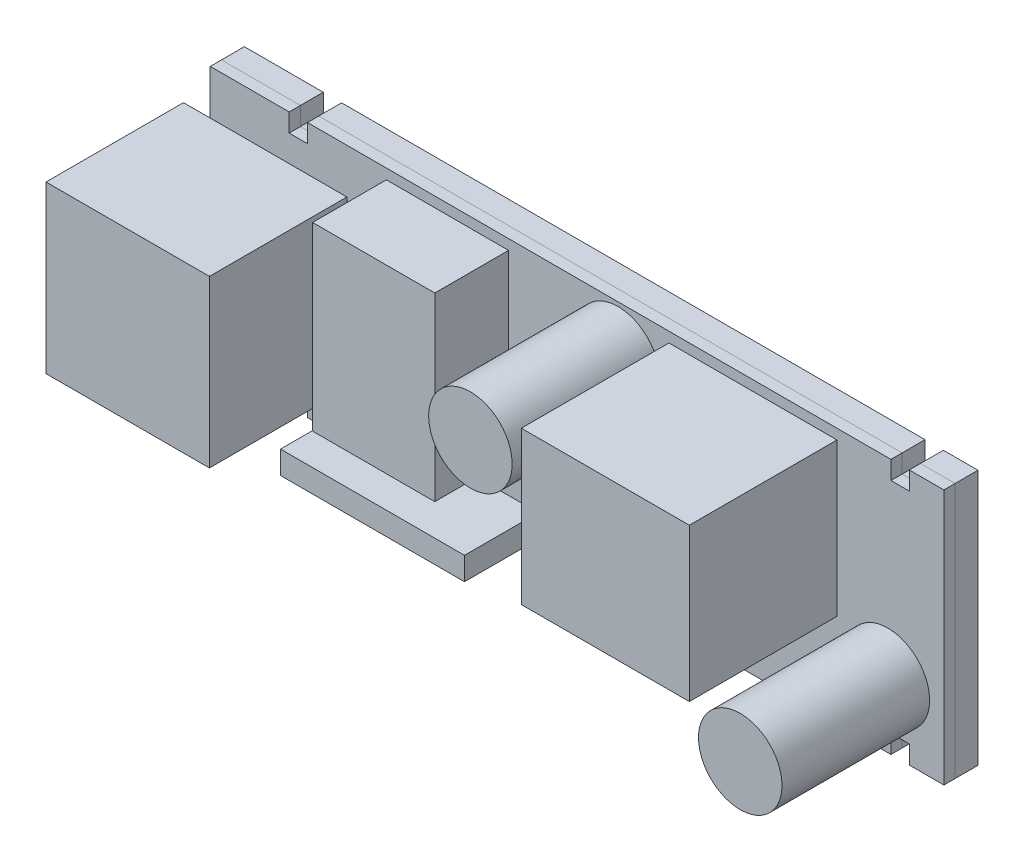
SolidWorks part; units mm, degrees
note: The reader was unsure of these and kept them because the rebuilt part matched: shared geometry of "Sketch1<3>", "Sketch2<4>", "Sketch2<5>".
ref_plane "Front Plane" through (0, 0, 0) normal (0, 0, 1) x (1, 0, 0)
ref_plane "Top Plane" through (0, 0, 0) normal (0, 1, 0) x (1, 0, 0)
ref_plane "Right Plane" through (0, 0, 0) normal (1, 0, 0) x (0, 0, -1)
sketch "Sketch1" plane through (0, 0, 0) normal (0, 0, 1) x (1, 0, 0)
  line L0 (-36.675, 12.55) -> (35.375, 12.55) construction
  line L1 (35.375, 12.55) -> (35.375, -12.55) construction
  line L2 (35.375, -12.55) -> (-36.675, -12.55) construction
  line L3 (-36.675, -12.55) -> (-36.675, 12.55) construction
  line L4 (-36.675, 12.55) -> (-36.675, -12.55)
  line L5 (-36.675, -12.55) -> (-28.925, -12.55)
  line L6 (-28.925, -12.55) -> (-28.925, -10.75)
  line L7 (-28.925, -10.75) -> (-27.125, -10.75)
  line L8 (-27.125, -10.75) -> (-27.125, -12.55)
  line L9 (-27.125, -12.55) -> (30.175, -12.55)
  line L10 (30.175, -12.55) -> (30.175, -10.75)
  line L11 (30.175, -10.75) -> (31.975, -10.75)
  line L12 (31.975, -10.75) -> (31.975, -12.55)
  line L13 (31.975, -12.55) -> (35.375, -12.55)
  line L14 (35.375, -12.55) -> (35.375, 12.55)
  line L15 (35.375, 12.55) -> (31.975, 12.55)
  line L16 (31.975, 12.55) -> (31.975, 10.75)
  line L17 (31.975, 10.75) -> (30.175, 10.75)
  line L18 (30.175, 10.75) -> (30.175, 12.55)
  line L19 (30.175, 12.55) -> (-27.125, 12.55)
  line L20 (-27.125, 12.55) -> (-27.125, 10.75)
  line L21 (-27.125, 10.75) -> (-28.925, 10.75)
  line L22 (-28.925, 10.75) -> (-28.925, 12.55)
  line L23 (-28.925, 12.55) -> (-36.675, 12.55)
  line L24 (35.375, 0) -> (0, 0) construction
  line L25 (39.6275, 0) -> (-39.6275, 0) construction
  line L26 (0, -13.805) -> (0, 13.805) construction
  circle A0 centre (0, 0) radius 1.375
  dimension "D7" = 2.75
  dimension "D1" = 1.8
  dimension "D2" = 1.8
  dimension "D3" = 3.4
  dimension "D4" = 7.75
  dimension "D5" = 25.1
  dimension "D6" = 72.05
  dimension "D8" = 35.375
extrude "Boss-BoardThk" add sketch "Sketch1" along normal blind 1.1 contours L19 L20 L21 L22 L23 L4 L5 L6 L7 L8 L9 L10 L11 L12 L13 L14 L15 L16 L17 L18 | A0
extrude "Boss-LowerClearance" add sketch "Sketch1<3>" against normal blind 2.25 separate body contours A0
sketch "Sketch1<3>" plane through (0, 0, 0) normal (0, 0, 1) x (1, 0, 0) same geometry as "Sketch1"
sketch "Sketch2" plane through (0, 0, 1.1) normal (0, 0, 1) x (1, 0, 0)
  line L0 (35.375, -12.55) -> (35.375, 12.55) construction
  line L1 (-19.375, 11.55) -> (-7.375, 11.55)
  line L2 (-19.375, 11.55) -> (-19.375, -6.2)
  line L3 (-19.375, -6.2) -> (-7.375, -6.2)
  line L4 (-7.375, 11.55) -> (-7.375, -6.2)
  line L5 (8.375, 11.55) -> (24.875, 11.55)
  line L6 (8.375, 11.55) -> (8.375, -3.45)
  line L7 (8.375, -3.45) -> (24.875, -3.45)
  line L8 (24.875, 11.55) -> (24.875, -3.45)
  line L9 (-23.255, 8.15) -> (-39.305, 8.15)
  line L10 (-23.255, 8.15) -> (-23.255, -8.15)
  line L11 (-23.255, -8.15) -> (-39.305, -8.15)
  line L12 (-39.305, 8.15) -> (-39.305, -8.15)
  line L13 (-23.255, 0) -> (-39.305, 0) construction
  line L14 (31.975, -12.55) -> (35.375, -12.55) construction
  line L15 (30.175, 12.55) -> (-27.125, 12.55) construction
  line L16 (-36.675, 12.55) -> (-36.675, -12.55) construction
  line L17 (-27.125, -12.55) -> (30.175, -12.55) construction
  line L18 (-22.525, -9.3) -> (-4.455, -9.3)
  line L19 (-22.525, -9.3) -> (-22.525, -11.55)
  line L20 (-22.525, -11.55) -> (-4.455, -11.55)
  line L21 (-4.455, -9.3) -> (-4.455, -11.55)
  line L22 (35.375, 0) -> (0, 0) construction
  circle A0 centre (29.875, -6.05) radius 4.1
  circle A1 centre (3.375, 8.05) radius 4.1
  dimension "D1" = 8.2
  dimension "D2" = 15
  dimension "D3" = 16.5
  dimension "D4" = 5
  dimension "D5" = 5
  dimension "D6" = 5.5
  dimension "D7" = 6.5
  dimension "D8" = 4.5
  dimension "D9" = 17.3
  dimension "D10" = 1
  dimension "D11" = 17.75
  dimension "D12" = 2.25
  dimension "D13" = 18.07
  dimension "D14" = 14.15
  dimension "D15" = 1
  dimension "D16" = 16.3
  dimension "D17" = 16.05
  dimension "D18" = 2.63
  dimension "D19" = 12
  dimension "D20" = 1
extrude "Boss-Extrude3" add sketch "Sketch2" along normal blind 14.5 separate body contours A0 | A1 | L7 L8 L5 L6
extrude "Boss-Extrude4" add sketch "Sketch2<4>" along normal blind 7.25 contours L3 L4 L1 L2 | L21 L20 L19 L18
sketch "Sketch2<4>" plane through (0, 0, 1.1) normal (0, 0, 1) x (1, 0, 0) same geometry as "Sketch2"
extrude "Boss-Extrude5" add sketch "Sketch2<5>" along normal blind 13.5 contours L11 L12 L9 L10
sketch "Sketch2<5>" plane through (0, 0, 1.1) normal (0, 0, 1) x (1, 0, 0) same geometry as "Sketch2"
equation "\"D8@Sketch1\"=34+0.5*(2.75)"
